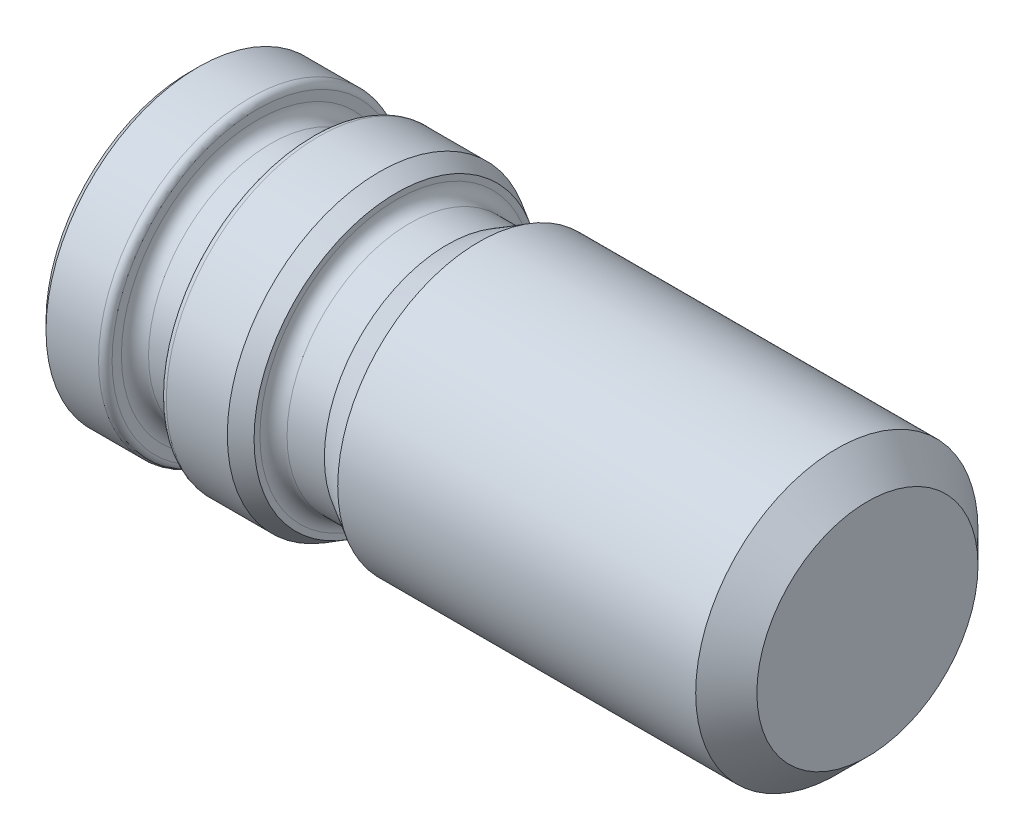
SolidWorks part; units mm, degrees
material "4140 H/T"
ref_plane "Front Plane" through (0, 0, 0) normal (0, 0, 1) x (1, 0, 0)
ref_plane "Top Plane" through (0, 0, 0) normal (0, 1, 0) x (1, 0, 0)
ref_plane "Right Plane" through (0, 0, 0) normal (1, 0, 0) x (0, 0, -1)
sketch "Sketch1" plane through (0, 0, 0) normal (0, 0, 1) x (1, 0, 0)
  line L0 (0, 0) -> (0, 6.525)
  line L1 (0, 6.525) -> (-1.805, 8.33)
  line L2 (-1.805, 8.33) -> (-22.9294, 8.33)
  line L3 (-22.9294, 8.33) -> (-24.8, 7.25)
  line L4 (-24.8, 7.25) -> (-27, 7.25)
  line L5 (-27.8, 8.05) -> (-27.8, 8.975)
  line L6 (-27.8, 8.975) -> (-32.4, 8.975)
  line L7 (-32.8, 8.575) -> (-32.8, 8.025)
  line L8 (-33.6, 7.225) -> (-35.2, 7.225)
  line L9 (-36, 8.025) -> (-36, 8.575)
  line L10 (-36.4, 8.975) -> (-40, 8.975)
  line L11 (-40, 8.975) -> (-40, 0)
  line L12 (-40, 0) -> (0, 0)
  line L13 (0, 0) -> (15.3627, 0) construction
  arc A0 (-32.8, 8.025) -> (-33.6, 7.225) centre (-33.6, 8.025) cw
  arc A1 (-35.2, 7.225) -> (-36, 8.025) centre (-35.2, 8.025) cw
  arc A2 (-32.4, 8.975) -> (-32.8, 8.575) centre (-32.4, 8.575) ccw
  arc A3 (-36, 8.575) -> (-36.4, 8.975) centre (-36.4, 8.575) ccw
  arc A4 (-27, 7.25) -> (-27.8, 8.05) centre (-27, 8.05) cw
  point P17 (-32.8, 7.225)
  point P20 (-36, 7.225)
  dimension "D13" = 0.8
  dimension "D14" = 0.4
  dimension "D15" = 0.8
  dimension "D1" = 40
  dimension "D2" = 17.95
  dimension "D3" = 14.45
  dimension "D4" = 3.2
  dimension "D5" = 4
  dimension "D6" = 12.2
  dimension "D7" = 16.66
  dimension "D8" = 14.5
  dimension "D9" = 30
  dimension "D10" = 3
  dimension "D11" = 45
  dimension "D12" = 13.05
revolve "Revolve1" add sketch "Sketch1" angle 360 about L13
cosmetic thread "Cosmetic Thread1" parameters "D2"=14.95
sketch "Sketch2" plane through (-40, 0, 0) normal (-1, 0, 0) x (0, 0, 1)
  line L1 (2.3671, 4.1) -> (-2.3671, 4.1)
  line L2 (-2.3671, 4.1) -> (-4.7343, 0)
  line L3 (-4.7343, 0) -> (-2.3671, -4.1)
  line L4 (-2.3671, -4.1) -> (2.3671, -4.1)
  line L5 (2.3671, -4.1) -> (4.7343, 0)
  line L6 (4.7343, 0) -> (2.3671, 4.1)
  circle A0 centre (0, 0) radius 4.1 construction
  dimension "D1" = 8.2
extrude "Cut-Extrude1" cut sketch "Sketch2" against normal blind 8
chamfer "Chamfer1" distance 0.5 angle 45 6 edges at (-40, 2.05, -3.5507) (-40, -2.05, -3.5507) (-40, -4.1, 0) (-40, -2.05, 3.5507) (-40, 2.05, 3.5507) (-40, 4.1, 0)
chamfer "Chamfer2" distance 0.5 angle 45 1 edges at (-40, 0, 8.975)
chamfer "Chamfer3" distance 1 angle 30 1 edges at (-27.8, 0, 8.975) first distance on face at (-32.4, 0, 8.975)
